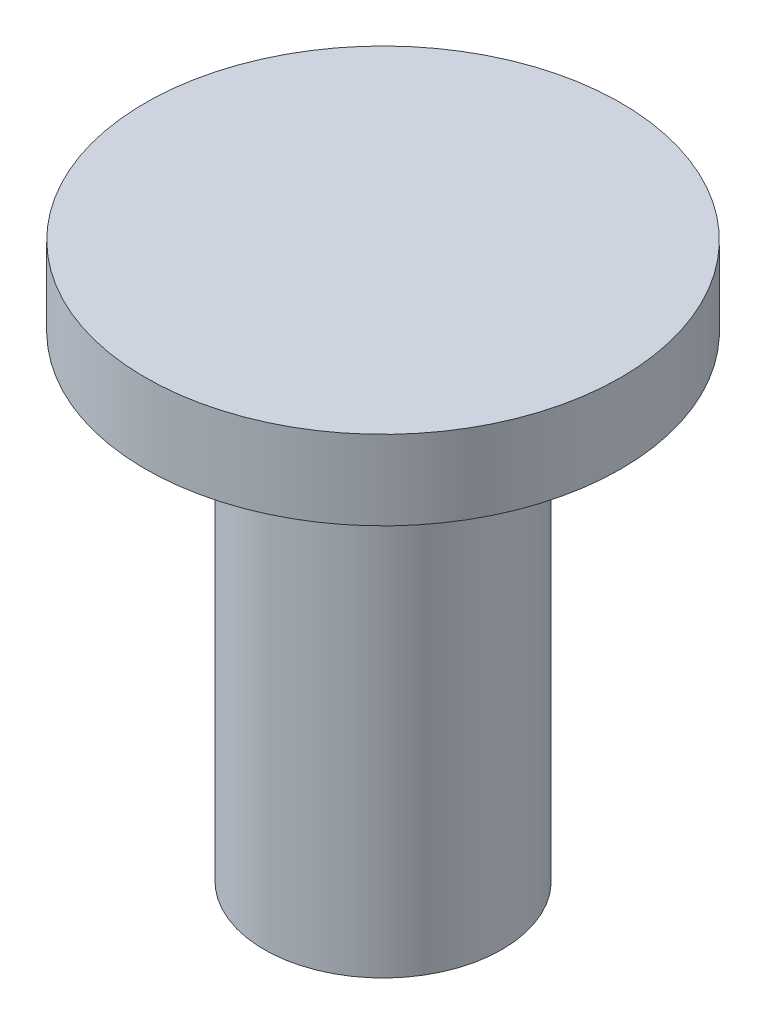
SolidWorks part; units mm, degrees
material "Бронза оловянная"
ref_plane "Спереди" through (0, 0, 0) normal (0, 0, 1) x (1, 0, 0)
ref_plane "Сверху" through (0, 0, 0) normal (0, 1, 0) x (1, 0, 0)
ref_plane "Справа" through (0, 0, 0) normal (1, 0, 0) x (0, 0, -1)
other "Configuration Table"
sketch "Sketch1" plane through (0, 0, 0) normal (0, 0, 1) x (1, 0, 0)
  line L1 (0, 0) -> (1.5, 0)
  line L2 (0, 0) -> (0, 6)
  line L3 (0, 6) -> (1.5, 6)
  line L4 (1.5, 0) -> (1.5, 6)
  line L5 (0, 6) -> (3, 6)
  line L6 (0, 6) -> (0, 7)
  line L7 (0, 7) -> (3, 7)
  line L8 (3, 6) -> (3, 7)
  line L9 (0, 7) -> (1.5, 7)
  line L10 (0, 7) -> (0, 6)
  line L11 (0, 6) -> (1.5, 6)
  line L12 (1.5, 7) -> (1.5, 6)
  dimension "1" = 1
  dimension "D2" = 3
  dimension "D3" = 1.5
  dimension "D4" = 6
revolve "Revolve1" add sketch "Sketch1" angle 360 about L6 region at (0.75, 3, 0) region at (0.75, 6.5, 0)
revolve "Revolve2" add sketch "Sketch1<3>" angle 360 about L6 region at (2.25, 6.5, 0)
sketch "Sketch1<3>" plane through (0, 0, 0) normal (0, 0, 1) x (1, 0, 0) same geometry as "Sketch1"
equation "\"length\" = 6"
equation "\"D4@Sketch1\"=\"length\""
